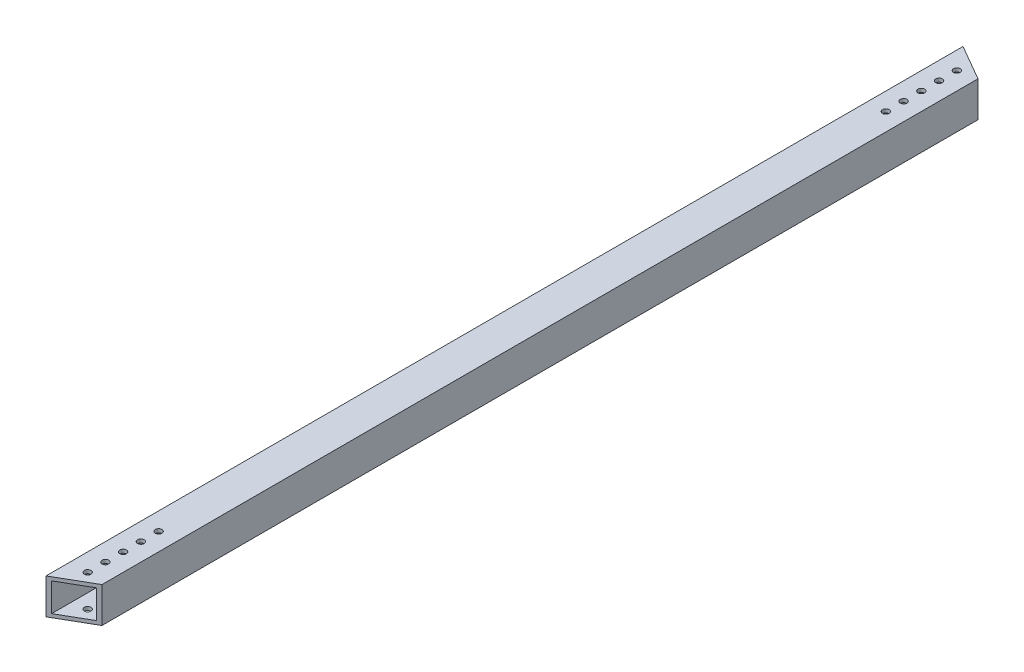
SolidWorks part; units mm, degrees
ref_plane "Front Plane" through (0, 0, 0) normal (0, 0, 1) x (1, 0, 0)
ref_plane "Top Plane" through (0, 0, 0) normal (0, 1, 0) x (1, 0, 0)
ref_plane "Right Plane" through (0, 0, 0) normal (1, 0, 0) x (0, 0, -1)
sketch "Sketch1" plane through (0, 0, 0) normal (0, 0, 1) x (1, 0, 0)
  line L0 (-10.16, 10.16) -> (10.16, 10.16)
  line L1 (-12.7, -12.7) -> (12.7, -12.7)
  line L2 (-12.7, -12.7) -> (-12.7, 12.7)
  line L3 (-12.7, 12.7) -> (12.7, 12.7)
  line L4 (12.7, -12.7) -> (12.7, 12.7)
  line L5 (-12.7, -12.7) -> (12.7, 12.7) construction
  line L6 (-12.7, 12.7) -> (12.7, -12.7) construction
  line L7 (10.16, -10.16) -> (10.16, 10.16)
  line L8 (-10.16, -10.16) -> (10.16, -10.16)
  line L9 (-10.16, -10.16) -> (-10.16, 10.16)
  point P0 (0, 0)
  dimension "D1" = 25.4
  dimension "D2" = 25.4
  dimension "D3" = 2.54
extrude "Boss-Extrude2" add sketch "Sketch1" along normal blind 656.5743
sketch "Sketch2" plane through (0, 12.7, 0) normal (0, 1, 0) x (1, 0, 0)
  line L0 (-12.7, -656.5743) -> (12.7, -641.9096)
  line L1 (12.7, -656.5743) -> (12.7, 0) construction
  line L2 (12.7, -641.9096) -> (12.7, -656.5743)
  line L3 (12.7, -656.5743) -> (-12.7, -656.5743)
  line L4 (-12.7, -328.2872) -> (12.7, -328.2872) construction
  line L5 (-12.7, -656.5743) -> (-12.7, 0) construction
  line L6 (12.7, 0) -> (-12.7, 0)
  line L7 (12.7, -14.6647) -> (12.7, 0)
  line L8 (-12.7, 0) -> (12.7, -14.6647)
  dimension "D1" = 30
extrude "Cut-Extrude1" cut sketch "Sketch2" against normal through all
sketch "Sketch3" plane through (0, 12.7, 0) normal (0, 1, 0) x (1, 0, 0)
  line L0 (0, -7.3323) -> (0, -649.242) construction
  line L1 (-12.7, 0) -> (12.7, -14.6647) construction
  line L2 (12.7, -641.9096) -> (-12.7, -656.5743) construction
  line L3 (12.7, -328.2872) -> (-12.7, -328.2872) construction
  line L4 (12.7, -641.9096) -> (12.7, -14.6647) construction
  line L5 (-12.7, -656.5743) -> (-12.7, 0) construction
  circle A5 centre (0, -639.4372) radius 2.3813
  circle A6 centre (0, -626.7372) radius 2.3813
  circle A7 centre (0, -614.0372) radius 2.3813
  circle A8 centre (0, -601.3372) radius 2.3813
  circle A9 centre (0, -588.6372) radius 2.3813
  circle A10 centre (0, -67.9372) radius 2.3812
  circle A11 centre (0, -55.2372) radius 2.3812
  circle A12 centre (0, -42.5372) radius 2.3812
  circle A13 centre (0, -29.8372) radius 2.3813
  circle A14 centre (0, -17.1372) radius 2.3813
  dimension "D3" = 4.7625
  dimension "D5" = 5
extrude "Cut-Extrude2" cut sketch "Sketch3" against normal through all
